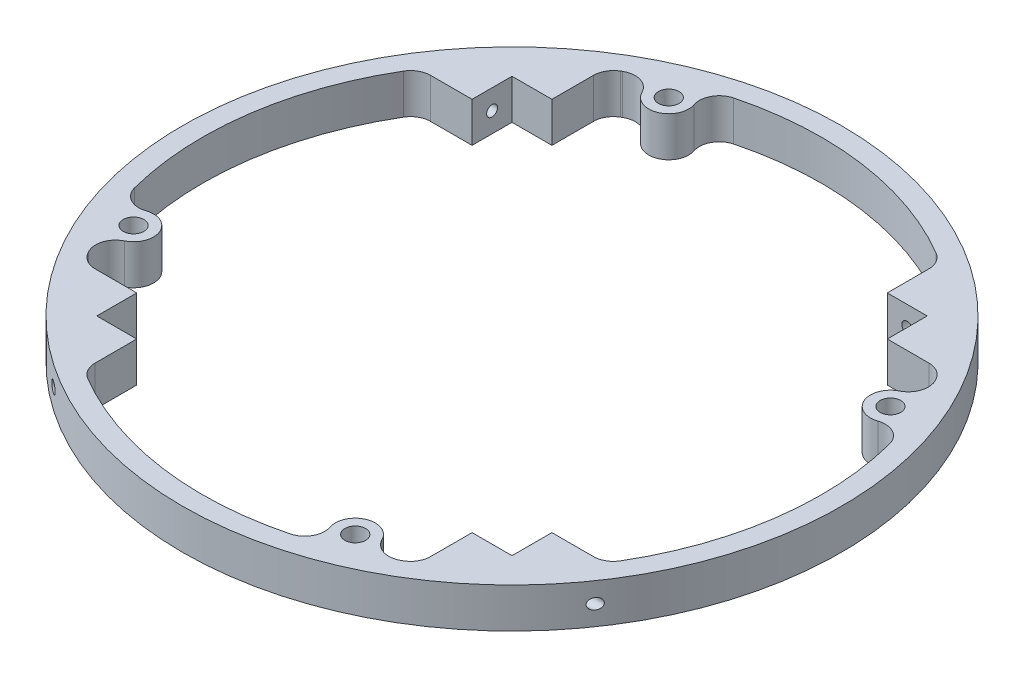
SolidWorks part; units mm, degrees
ref_plane "Front Plane" through (0, 0, 0) normal (0, 0, 1) x (1, 0, 0)
ref_plane "Top Plane" through (0, 0, 0) normal (0, 1, 0) x (1, 0, 0)
ref_plane "Right Plane" through (0, 0, 0) normal (1, 0, 0) x (0, 0, -1)
sketch "Sketch1" plane through (0, 0, 0) normal (0, 1, 0) x (1, 0, 0)
  line L0 (0, 0) -> (0, 84.2831) construction
  line L1 (-52, 52) -> (52, 52) construction
  line L2 (-52, 52) -> (-52, -52) construction
  line L3 (-52, -52) -> (52, -52) construction
  line L4 (52, 52) -> (52, -52) construction
  line L5 (0, 0) -> (-99.9306, 0) construction
  line L6 (0, 0) -> (-52, 52) construction
  line L7 (0, 0) -> (-31.8699, 76.9407) construction
  line L8 (-42, 52) -> (-52, 52)
  line L9 (-52, 52) -> (-52, 42)
  line L10 (-52, 42) -> (-65.192, 42)
  line L11 (-42, 52) -> (-42, 65.192)
  line L12 (-34.2348, 69.5844) -> (-32.3831, 65.114)
  line L13 (-24.996, 73.4112) -> (-23.1443, 68.9409)
  line L14 (42, 52) -> (42, 65.192)
  line L15 (52, 52) -> (42, 52)
  line L16 (52, 42) -> (52, 52)
  line L17 (52, 42) -> (65.192, 42)
  line L18 (69.5844, 34.2348) -> (65.114, 32.3831)
  line L19 (73.4112, 24.996) -> (68.9409, 23.1443)
  line L20 (52, -42) -> (65.192, -42)
  line L21 (52, -52) -> (52, -42)
  line L22 (42, -52) -> (52, -52)
  line L23 (42, -52) -> (42, -65.192)
  line L24 (34.2348, -69.5844) -> (32.3831, -65.114)
  line L25 (24.996, -73.4112) -> (23.1443, -68.9409)
  line L26 (-42, -52) -> (-42, -65.192)
  line L27 (-52, -52) -> (-42, -52)
  line L28 (-52, -42) -> (-52, -52)
  line L29 (-52, -42) -> (-65.192, -42)
  line L30 (-69.5844, -34.2348) -> (-65.114, -32.3831)
  line L31 (-73.4112, -24.996) -> (-68.9409, -23.1443)
  circle A0 centre (0, 0) radius 82.55
  arc A1 (-65.192, 42) -> (-77.55, 0) centre (0, 0) ccw
  arc A2 (-42, 65.192) -> (-34.2348, 69.5844) centre (0, 0) cw
  arc A3 (-32.3831, 65.114) -> (-23.1443, 68.9409) centre (-27.7637, 67.0275) ccw
  arc A4 (0, 77.55) -> (-24.996, 73.4112) centre (0, 0) ccw
  arc A5 (42, 65.192) -> (0, 77.55) centre (0, 0) ccw
  arc A6 (65.192, 42) -> (69.5844, 34.2348) centre (0, 0) cw
  arc A7 (65.114, 32.3831) -> (68.9409, 23.1443) centre (67.0275, 27.7637) ccw
  arc A8 (77.55, 0) -> (73.4112, 24.996) centre (0, 0) ccw
  arc A9 (65.192, -42) -> (77.55, 0) centre (0, 0) ccw
  arc A10 (42, -65.192) -> (34.2348, -69.5844) centre (0, 0) cw
  arc A11 (32.3831, -65.114) -> (23.1443, -68.9409) centre (27.7637, -67.0275) ccw
  arc A12 (0, -77.55) -> (24.996, -73.4112) centre (0, 0) ccw
  arc A13 (-42, -65.192) -> (0, -77.55) centre (0, 0) ccw
  arc A14 (-65.192, -42) -> (-69.5844, -34.2348) centre (0, 0) cw
  arc A15 (-65.114, -32.3831) -> (-68.9409, -23.1443) centre (-67.0275, -27.7637) ccw
  arc A16 (-77.55, 0) -> (-73.4112, -24.996) centre (0, 0) ccw
  point P21 (-24.0701, 71.176)
  point P61 (0, 0)
  dimension "D1" = 165.1
  dimension "D2" = 104
  dimension "D3" = 22.5
  dimension "D4" = 5
  dimension "D5" = 72.55
  dimension "D6" = 10
  dimension "D7" = 10
  dimension "D8" = 4
extrude "Boss-Extrude1" add sketch "Sketch1" along normal blind 10
fillet "Fillet1" radius 5 16 edges at (-73.4112, 5, 24.996) (-69.5844, 5, 34.2348) (-42, 5, 65.192) (-65.192, 5, 42) (24.996, 5, 73.4112) (34.2348, 5, 69.5844) (42, 5, 65.192) (65.192, 5, 42) (73.4112, 5, -24.996) (69.5844, 5, -34.2348) (65.192, 5, -42) (42, 5, -65.192) (-34.2348, 5, -69.5844) (-24.996, 5, -73.4112) (-42, 5, -65.192) (-65.192, 5, -42)
hole_wizard "#6 (0.204) Diameter Hole1" positions "Sketch4" profile "Sketch3" hole size "#6" standard "ANSI Inch" end condition through all
sketch "Sketch4" plane through (0, 10, 0) normal (0, 1, 0) x (1, 0, 0)
  point P0 (67.0275, 27.7637)
sketch "Sketch3" plane through (67.0275, 10, -27.7637) normal (1, 0, 0) x (0, 0, 1)
  line L0 (0, 0) -> (0, 10)
  line L1 (0, 10) -> (2.5908, 10)
  line L2 (2.5908, 10) -> (2.5908, 0)
  line L5 (2.5908, 0) -> (0, 0)
  line L11 (0, -6.35) -> (0, 107.95) construction
  dimension "Thru Hole Dia." = 5.1816
  dimension "Thru Hole Depth" = 10
hole_wizard "#6-32 Tapped Hole2" positions "Sketch8" profile "Sketch9" tap size "#6-32" standard "ANSI Inch" end condition through all
sketch "Sketch8" plane through (0, 0, -52) normal (0, 0, 1) x (1, 0, 0)
  line L0 (52, 0) -> (42, 10)
  point P0 (47, 5)
  point P10 (47, 5)
sketch "Sketch9" plane through (47, 5, -52) normal (1, 0, 0) x (0, -1, 0)
  line L0 (0, 0) -> (0, 30.55)
  line L1 (0, 30.55) -> (1.3525, 30.55)
  line L2 (1.3525, 30.55) -> (1.3525, 0)
  line L5 (1.3525, 0) -> (0, 0)
  line L11 (0, -6.35) -> (0, 107.95) construction
  dimension "Thru Tap Drill Dia." = 2.7051
  dimension "Thru Tap Drill Depth" = 30.55
cosmetic thread "Hole Thread2" parameters "D2"=3.5052
ref_axis "Axis1" through (0, 10.5, 0) along (0, -1, 0)
pattern_circular "CirPattern1" count 4 over 360 about axis through (0, 10.5, 0) along (0, -1, 0) of "#6 (0.204) Diameter Hole1", "#6-32 Tapped Hole2"
equation "\"TubeDiameter\" = 6.500in"
equation "\"D1@Sketch1\"=\"TubeDiameter\""
equation "\"D5@Sketch1\"=\"TubeDiameter\"/2-10mm"
